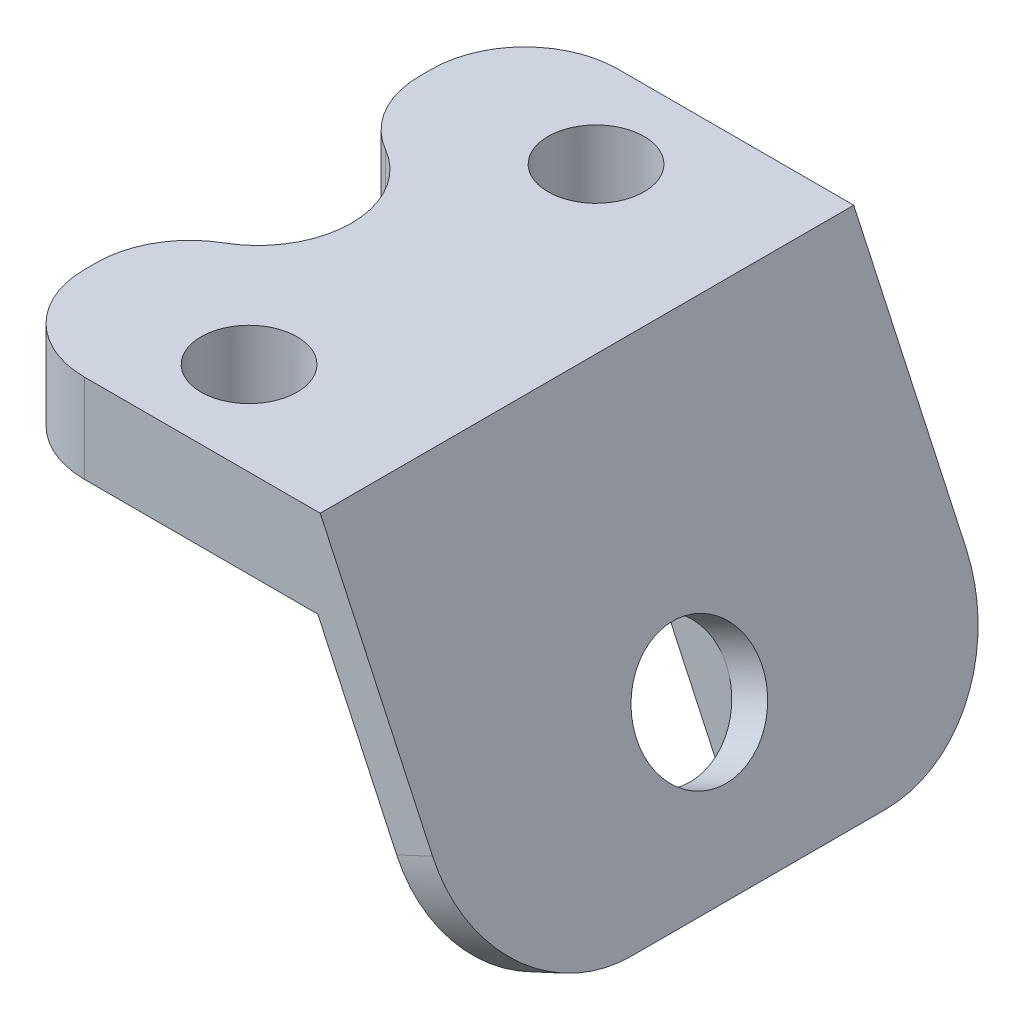
SolidWorks part; units mm, degrees
ref_plane "Front Plane" through (0, 0, 0) normal (0, 0, 1) x (1, 0, 0)
ref_plane "Top Plane" through (0, 0, 0) normal (0, 1, 0) x (1, 0, 0)
ref_plane "Right Plane" through (0, 0, 0) normal (1, 0, 0) x (0, 0, -1)
sketch "Sketch1" plane through (0, 0, 0) normal (0, 0, 1) x (1, 0, 0)
  line L0 (0, 0) -> (0, 4.826)
  line L1 (0, 4.826) -> (17.9118, 4.826)
  line L2 (17.9118, 4.826) -> (27.2509, -15.2017)
  line L3 (27.2509, -15.2017) -> (25.2942, -16.1142)
  line L4 (25.2942, -16.1142) -> (17.78, 0)
  line L5 (17.78, 0) -> (0, 0)
  dimension "D1" = 4.826
  dimension "D2" = 17.78
  dimension "D3" = 17.78
  dimension "D4" = 115
  dimension "D5" = 2.159
extrude "Boss-Extrude1" add sketch "Sketch1" along normal blind 29.0576
sketch "Sketch3" plane through (14.6044, 6.8101, 0) normal (-0.9063, -0.4226, 0) x (0.4226, -0.9063, 0)
  line L0 (7.5142, 14.5288) -> (25.2942, 14.5288) construction
  line L9 (7.5142, 29.0576) -> (7.5142, 0) construction
  line L10 (25.2942, 29.0576) -> (25.2942, 0) construction
  line L12 (10.0542, 21.7678) -> (25.2942, 21.7678)
  line L13 (10.0542, 21.7678) -> (10.0542, 17.9578)
  line L14 (10.0542, 17.9578) -> (25.2942, 17.9578)
  line L15 (25.2942, 21.7678) -> (25.2942, 17.9578)
  line L16 (10.0542, 21.7678) -> (25.2942, 17.9578) construction
  line L17 (10.0542, 17.9578) -> (25.2942, 21.7678) construction
  line L18 (10.0542, 7.2898) -> (25.2942, 7.2898)
  line L19 (10.0542, 7.2898) -> (10.0542, 11.0998)
  line L20 (10.0542, 11.0998) -> (25.2942, 11.0998)
  line L21 (25.2942, 7.2898) -> (25.2942, 11.0998)
  line L22 (10.0542, 7.2898) -> (25.2942, 11.0998) construction
  line L23 (10.0542, 11.0998) -> (25.2942, 7.2898) construction
  circle A1 centre (17.6742, 14.5288) radius 3.429
  point P8 (17.6742, 19.8628)
  point P13 (17.6742, 9.1948)
  dimension "D1" = 6.858
  dimension "D4" = 7.62
  dimension "D2" = 3.81
  dimension "D3" = 15.24
extrude "Cut-Extrude2" cut sketch "Sketch3" against normal through all contours A1
extrude "Boss-Extrude2" add sketch "Sketch3<3>" along normal blind 2.54 contours L12 L15 L14 L13 | L20 L21 L18 L19
sketch "Sketch3<3>" plane through (14.6044, 6.8101, 0) normal (-0.9063, -0.4226, 0) x (0.4226, -0.9063, 0) same geometry as "Sketch3"
sketch "Sketch2" plane through (0, 4.826, 0) normal (0, 1, 0) x (1, 0, 0)
  line L0 (17.9118, 0) -> (0, 0) construction
  line L1 (8.9559, -5.08) -> (8.9559, -23.9776) construction
  line L2 (0, -14.5288) -> (17.9118, -14.5288) construction
  line L3 (0, -29.0576) -> (0, 0) construction
  line L4 (17.9118, -29.0576) -> (17.9118, 0) construction
  circle A0 centre (8.9559, -5.08) radius 2.6162
  circle A1 centre (8.9559, -23.9776) radius 2.6162
  point P4 (8.9559, 0)
  point P5 (8.9559, -14.5288)
  dimension "D1" = 5.2324
  dimension "D2" = 18.8976
extrude "Cut-Extrude1" cut sketch "Sketch2" against normal through all
fillet "Fillet7" radius 5.08 2 edges at (0, 2.413, 0) (0, 2.413, 29.0576)
fillet "Fillet8" radius 7.62 2 edges at (26.2725, -15.6579, 0) (26.2725, -15.6579, 29.0576)
sketch "Sketch4" plane through (0, 4.826, 0) normal (0, 1, 0) x (1, 0, 0)
  line L0 (0, -23.9776) -> (0, -5.08) construction
  circle A0 centre (0, -14.5288) radius 5.08
  dimension "D1" = 10.16
extrude "Cut-Extrude3" cut sketch "Sketch4" against normal blind 10.16
fillet "Fillet9" radius 5.08 2 edges at (0, 2.413, 19.6088) (0, 2.413, 9.4488)
